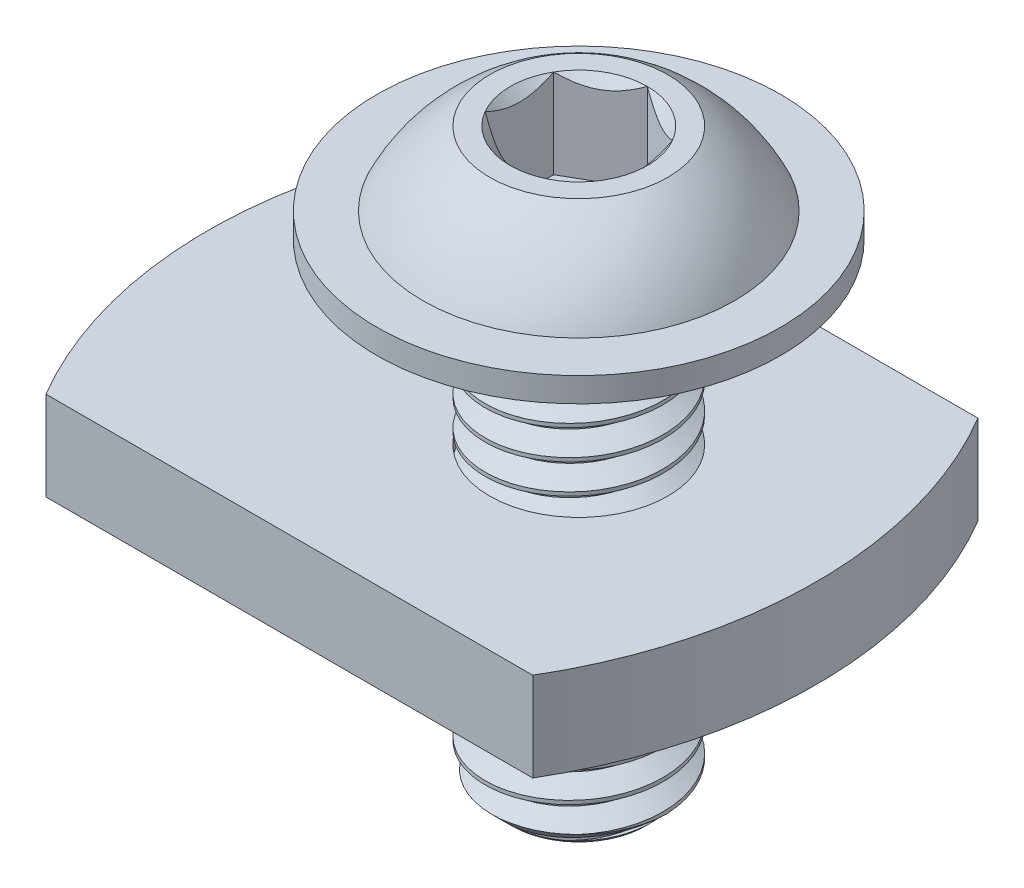
SolidWorks part; units mm, degrees
note: '?' marks a value the reader was unsure of.
ref_plane "Front Plane" through (0, 0, 0) normal (0, 0, 1) x (1, 0, 0)
ref_plane "Top Plane" through (0, 0, 0) normal (0, 1, 0) x (1, 0, 0)
ref_plane "Right Plane" through (0, 0, 0) normal (1, 0, 0) x (0, 0, -1)
sketch "Sketch1" plane through (0, 0, 0) normal (0, 1, 0) x (1, 0, 0)
  circle A0 centre (0, 0) radius 3
  point P3 (-3, 0)
  point P4 (3, 0)
  dimension "D1" = 6
extrude "Boss-Extrude1" add sketch "Sketch1" against normal blind 16
sketch "Sketch2" plane through (0, -16, 0) normal (0, -1, 0) x (1, 0, 0)
  circle A1 centre (0, 0) radius 3
  circle A2 centre (0, 0) radius 3
  point P0 (0, -3)
  dimension "D1" = 0
curve "Helix/Spiral1" pitch 1 height 17 turns 17 parameters "Pitch"=1
sketch "Sketch3" plane through (0, 0, 0) normal (1, 0, 0) x (0, 0, -1)
  line L0 (3.1083, -15.9375) -> (2.2422, -16.4375) construction
  line L1 (2.2422, -16.4375) -> (3.1083, -16.9375) construction
  line L2 (3.1083, -16.9375) -> (3.1083, -15.9375) construction
  line L3 (2.3505, -16.375) -> (2.3505, -16.5) construction
  line L4 (3, -16) -> (3, -16.875) construction
  line L5 (2.2422, -16.4375) -> (2.3505, -16.4375) construction
  line L6 (3, -16.4375) -> (3.1083, -16.4375) construction
  line L8 (2.2422, -16.4375) -> (-3, -16.4375) construction
  line L9 (2.3505, -16.375) -> (3.0541, -15.9687)
  line L10 (2.3505, -16.375) -> (2.3505, -16.5)
  line L11 (2.3505, -16.5) -> (3.0541, -16.9062)
  line L12 (3.0541, -16.9062) -> (3.0541, -15.9687)
  line L14 (-3, -16.4375) -> (-3, -15.4375) construction
  line L15 (-3, -15.4375) -> (-3, -14.4375) construction
  line L16 (-3, -14.4375) -> (-3, -13.4375) construction
  line L17 (-3, -13.4375) -> (-3, -12.4375) construction
  line L18 (-3, 0) -> (-3, -16) construction
  point P15 (3.0541, -16.4375)
  dimension "D1" = 1
  dimension "D2" = 0.125
sketch "Sketch5" plane through (0, 0, 0) normal (0, 0, 1) x (1, 0, 0)
  line L0 (0, 0) -> (0, 3.3)
  line L1 (-6.8, 0) -> (0, 0)
  line L2 (0, 3.3) -> (-3, 3.3)
  line L3 (-5.25, 0.825) -> (-6.8, 0.825)
  line L4 (-6.8, 0.825) -> (-6.8, 0)
  line L5 (0, 0) -> (0, -16) construction
  arc A0 (-3, 3.3) -> (-5.25, 0.825) centre (0, -1.6875) ccw
  dimension "D1" = 3.3
  dimension "D2" = 0.825
  dimension "D3" = 13.6
  dimension "D4" = 10.5
revolve "Revolve1" add sketch "Sketch5" angle 360 mid plane about L0
sketch "Sketch6" plane through (0, 3.3, 0) normal (0, 1, 0) x (1, 0, 0)
  line L1 (0, 2.3094) -> (-2, 1.1547)
  line L2 (-2, 1.1547) -> (-2, -1.1547)
  line L3 (-2, -1.1547) -> (0, -2.3094)
  line L4 (0, -2.3094) -> (2, -1.1547)
  line L5 (2, -1.1547) -> (2, 1.1547)
  line L6 (2, 1.1547) -> (0, 2.3094)
  circle A0 centre (0, 0) radius 2 construction
  dimension "D1" = 4
extrude "Cut-Extrude2" cut sketch "Sketch6" against normal blind 3
sketch "Sketch7" plane through (0, 3.3, 0) normal (0, 1, 0) x (1, 0, 0)
  circle A0 centre (0, 0) radius 2.3094
extrude "Cut-Extrude3" cut sketch "Sketch7" against normal blind 3 draft 45
sketch "Sketch8" plane through (0, 0, 0) normal (0, 1, 0) x (1, 0, 0)
  line L0 (-12.5, 0) -> (0, 0) construction
  line L1 (0, 0) -> (8, 0) construction
  line L2 (-10.45, 7.5) -> (5.95, 7.5)
  line L3 (-10.45, -7.5) -> (5.95, -7.5)
  line L4 (-12.5, 7.5) -> (8, 7.5) construction
  line L5 (-12.5, 7.5) -> (-12.5, -7.5) construction
  line L6 (-12.5, -7.5) -> (8, -7.5) construction
  line L7 (8, 7.5) -> (8, -7.5) construction
  arc A0 (-10.45, 7.5) -> (-10.45, -7.5) centre (2.2445, 0) ccw
  arc A1 (5.95, 7.5) -> (5.95, -7.5) centre (-6.7445, 0) cw
  circle A3 centre (0, 0) radius 3
  circle A4 centre (0, 0) radius 3
  dimension "D2" = 20.5
  dimension "D3" = 15
  dimension "D4" = 8
  dimension "D5" = 2.05
extrude "Boss-Extrude2" add sketch "Sketch8" against normal blind 3 from offset 6 separate body offset against normal yes
sketch "Sketch9" plane through (0, -9, 0) normal (0, -1, 0) x (1, 0, 0)
  circle A1 centre (0, 0) radius 3 construction
  circle A2 centre (0, 0) radius 3
  circle A3 centre (0, 0) radius 3.5
  dimension "D1" = 7
extrude "Boss-Extrude3" add sketch "Sketch9" along normal blind 1
chamfer "Chamfer1" distance 0.75 angle 45 1 edges at (0, -16, 3)
sweep "Cut-Sweep1" cut profiles "Sketch3" path "Helix/Spiral1"
ref_axis "Center Axis 1" through (0, -10, 0) along (0, 1, 0)?
ref_plane "Contact Plane 1" through (0, 0, 0) normal (0, -1, 0) x (-1, 0, 0)
ref_plane "Contact Plane 2" through (0, -6, 0) normal (0, 1, 0) x (1, 0, 0)
equation "\"D3@Helix/Spiral1\" = \"Pitch@Helix/Spiral1\" + \"D1@Boss-Extrude1\""
equation "\"D1@Sketch3\" = \"Pitch@Helix/Spiral1\""
equation "\"D2@Sketch3\" = \"D1@Sketch3\" / 8"
equation "\"D1@Cut-Extrude2\" = \"D1@Sketch6\" * 3/4"
equation "\"D1@Cut-Extrude3\" = \"D1@Cut-Extrude2\""
equation "\"D2@Sketch5\" = \"D1@Sketch5\" * 1/4"
equation "\"D5@Sketch8\" = \"D2@Sketch8\" * 1/10"
equation "\"D1@Chamfer1\"=\"Pitch@Helix/Spiral1\"*.75"
